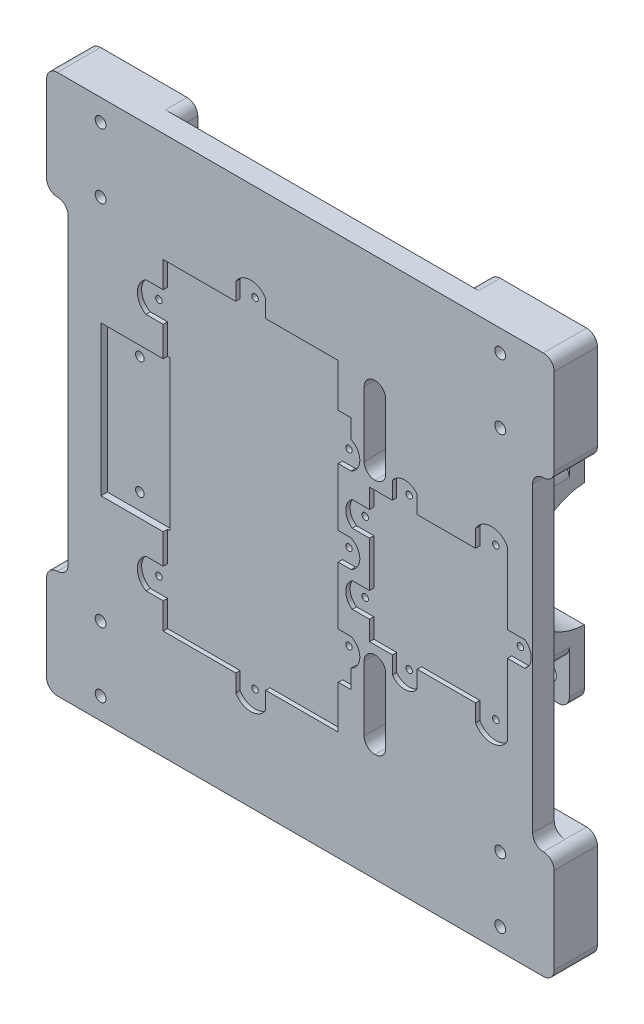
SolidWorks part; units mm, degrees
other "Marquage1"
sketch "Esquisse17" plane through (0, -52.2, -65) normal (-0.4358, -0.0146, -0.8999) x (-0.2736, 0.9547, 0.117)
ref_plane "Plan de face" through (0, 0, 0) normal (0, 0, 1) x (1, 0, 0)
ref_plane "Plan de dessus" through (0, 0, 0) normal (0, 1, 0) x (1, 0, 0)
ref_plane "Plan de droite" through (0, 0, 0) normal (1, 0, 0) x (0, 0, -1)
sketch "Esquisse1" plane through (0, 0, 0) normal (0, 0, 1) x (1, 0, 0)
  line L5 (235, 50) -> (235, 0)
  line L7 (0, 50) -> (0, 0)
  line L9 (235, 200) -> (235, 250)
  line L11 (0, 250) -> (0, 200)
  line L16 (225, 200) -> (225, 50)
  line L19 (147, 50) -> (157, 50)
  line L20 (225, 50) -> (235, 50)
  line L21 (225, 200) -> (235, 200)
  line L23 (10, 200) -> (10, 50)
  line L24 (0, 200) -> (10, 200)
  line L27 (10, 50) -> (0, 50)
  line L32 (0, 250) -> (235, 250)
  line L33 (0, 0) -> (235, 0)
  line L35 (147, 200) -> (157, 200)
  line L36 (147, 160) -> (157, 160)
  line L37 (147, 90) -> (157, 90)
  line L38 (147, 200) -> (147, 160)
  line L39 (157, 200) -> (157, 160)
  line L40 (147, 90) -> (147, 50)
  line L41 (157, 90) -> (157, 50)
  circle A0 centre (117.5, 125) radius 0.005
  dimension "D19" = 0.01
  dimension "D1" = 50
  dimension "D2" = 235
  dimension "D11" = 10
  dimension "D12" = 10
  dimension "D15" = 10
  dimension "D16" = 10
  dimension "D17" = 150
  dimension "D18" = 50
  dimension "D6" = 235
  dimension "D21" = 125
  dimension "D20" = 117.5
  dimension "D7" = 50
  dimension "D8" = 40
  dimension "D9" = 40
  dimension "D13" = 10
  dimension "D14" = 10
  dimension "D3" = 78
  dimension "D10" = 78
  dimension "D4" = 35
  dimension "D5" = 35
extrude "Boss.-Extru.2" add sketch "Esquisse1" along normal blind 10
sketch "Esquisse4" plane through (0, 0, 0) normal (0, 0, -1) x (-1, 0, 0)
  line L0 (0, 250) -> (0, 200) construction
  line L1 (0, 250) -> (-50, 250)
  line L2 (0, 250) -> (0, 200)
  line L4 (-50, 250) -> (-50, 200)
  line L5 (-117.5, 250) -> (-117.5, 0) construction
  line L6 (0, 0) -> (-235, 0) construction
  line L7 (-235, 200) -> (-185, 200)
  line L8 (-235, 250) -> (-235, 200)
  line L9 (-185, 250) -> (-185, 200)
  line L10 (-235, 250) -> (-185, 250)
  line L11 (-225, 125) -> (-10, 125) construction
  line L12 (-225, 50) -> (-225, 200) construction
  line L21 (-10, 200) -> (-10, 50) construction
  line L22 (0, 200) -> (-50, 200)
  line L24 (-235, 250) -> (0, 250) construction
  line L25 (0, 250) -> (0, 200) construction
  line L26 (-235, 50) -> (-185, 50)
  line L27 (-185, 0) -> (-185, 50)
  line L28 (-235, 0) -> (-235, 50)
  line L29 (-235, 0) -> (-185, 0)
  line L30 (0, 50) -> (-50, 50)
  line L31 (0, 0) -> (0, 50)
  line L32 (-50, 0) -> (-50, 50)
  line L33 (0, 0) -> (-50, 0)
  dimension "D1" = 50
  dimension "D2" = 50
extrude "Boss.-Extru.3" add sketch "Esquisse4" along normal blind 10
sketch "Esquisse6" plane through (0, 0, 0) normal (0, 0, -1) x (-1, 0, 0)
  line L0 (-225, 50) -> (-225, 200) construction
  line L1 (-127, 164) -> (-107, 164)
  line L2 (-127, 164) -> (-127, 86)
  line L3 (-127, 86) -> (-107, 86)
  line L4 (-107, 164) -> (-107, 86)
  line L5 (-147, 90) -> (-147, 50) construction
  line L6 (-50, 200) -> (0, 200) construction
  line L7 (-10, 50) -> (-50, 50) construction
  line L10 (-225, 200) -> (-185, 200) construction
  line L11 (-195, 164) -> (-175, 164)
  line L12 (-195, 164) -> (-195, 86)
  line L13 (-195, 86) -> (-175, 86)
  line L14 (-175, 164) -> (-175, 86)
  line L15 (-185, 50) -> (-225, 50) construction
  dimension "D5" = 36
  dimension "D6" = 36
  dimension "D1" = 20
  dimension "D8" = 30
  dimension "D3" = 36
  dimension "D4" = 36
  dimension "D7" = 50
  dimension "D2" = 20
extrude "Boss.-Extru.5" add sketch "Esquisse6" along normal blind 45
fillet "Congé1" radius 5 20 edges at (50, 250, -5) (50, 200, -5) (185, 250, -5) (185, 200, -5) (235, 50, 0) (235, 200, 0) (0, 50, 0) (0, 200, 0) (225, 50, 5) (225, 200, 5) (10, 50, 5) (10, 200, 5) (235, 250, 0) (0, 250, 0) (0, 0, 0) (235, 0, 0) (50, 50, -5) (185, 50, -5) (185, 0, -5) (50, 0, -5)
sketch "Esquisse8" plane through (195, 0, 0) normal (1, 0, 0) x (0, 0, -1)
  line L0 (22.5, 164) -> (22.5, 86) construction
  line L2 (45, 125) -> (-10, 125) construction
  line L3 (45, 164) -> (45, 86) construction
  line L4 (0, 164) -> (0, 86) construction
  line L5 (-10, 55) -> (-10, 195) construction
  line L6 (45, 164) -> (0, 164) construction
  line L7 (45, 86) -> (0, 86) construction
  circle A0 centre (45, 125) radius 28.5
  dimension "D1" = 45
  dimension "D2" = 57
extrude "Enlèv. mat.-Extru.2" cut sketch "Esquisse8" against normal blind 100
sketch "Esquisse12" plane through (0, 164, 0) normal (0, 1, 0) x (1, 0, 0)
  line L10 (127, 45) -> (127, 0) construction
  line L11 (107, 45) -> (127, 45)
  line L12 (107, 45) -> (107, 37)
  line L13 (107, 37) -> (127, 37)
  line L14 (127, 45) -> (127, 37)
  line L15 (195, 45) -> (195, 0) construction
  line L16 (175, 45) -> (195, 45)
  line L17 (175, 45) -> (175, 37)
  line L18 (175, 37) -> (195, 37)
  line L19 (195, 45) -> (195, 37)
  dimension "D1" = 8
  dimension "D2" = 8
extrude "Boss.-Extru.6" add sketch "Esquisse12" along normal blind 20
sketch "Esquisse13" plane through (0, 86, 0) normal (0, -1, 0) x (1, 0, 0)
  line L0 (127, -45) -> (127, 0) construction
  line L1 (107, -45) -> (127, -45)
  line L2 (107, -45) -> (107, -37)
  line L3 (107, -37) -> (127, -37)
  line L4 (127, -45) -> (127, -37)
  line L5 (195, -45) -> (195, 0) construction
  line L6 (175, -45) -> (195, -45)
  line L7 (175, -45) -> (175, -37)
  line L8 (175, -37) -> (195, -37)
  line L9 (195, -45) -> (195, -37)
  dimension "D1" = 8
  dimension "D2" = 8
extrude "Boss.-Extru.7" add sketch "Esquisse13" along normal blind 20
fillet "Congé55" radius 5 16 edges at (107, 184, -41) (175, 184, -41) (175, 66, -41) (107, 66, -41) (127, 66, -41) (195, 66, -41) (175, 164, -18.5) (195, 164, -18.5) (127, 164, -18.5) (107, 164, -18.5) (107, 86, -18.5) (127, 86, -18.5) (175, 86, -18.5) (195, 86, -18.5) (195, 184, -41) (127, 184, -41)
sketch "Esquisse14" plane through (0, 0, -45) normal (0, 0, -1) x (-1, 0, 0)
  line L0 (-175, 153.5) -> (-127, 153.5) construction
  line L1 (-151, 153.5) -> (-151, 184.1356) construction
  line L2 (-175, 153.5) -> (-175, 179) construction
  line L3 (-195, 125) -> (-107, 125) construction
  line L4 (-195, 159) -> (-195, 91) construction
  line L5 (-107, 91) -> (-107, 159) construction
  circle A0 centre (-185, 173.5) radius 4
  circle A1 centre (-117, 173.5) radius 4
  circle A2 centre (-117, 76.5) radius 4
  circle A3 centre (-185, 76.5) radius 4
  dimension "D1" = 8
  dimension "D2" = 20
  dimension "D3" = 10
extrude "Enlèv. mat.-Extru.4" cut sketch "Esquisse14" against normal blind 10
sketch "Esquisse15" plane through (0, 66, 0) normal (0, -1, 0) x (1, 0, 0)
  line L5 (195, -37) -> (195, -45) construction
  line L6 (175, -45) -> (195, -45)
  line L7 (175, -45) -> (175, -44)
  line L8 (175, -44) -> (195, -44)
  line L9 (195, -45) -> (195, -44)
  dimension "D1" = 1
extrude "Enlèv. mat.-Extru.5" cut sketch "Esquisse15" against normal blind 120
sketch "Esquisse22" plane through (0, 0, 0) normal (0, 0, 1) x (1, 0, 0)
  line L0 (117.5, 250) -> (117.5, 0) construction
  line L1 (230, 250) -> (5, 250) construction
  line L2 (5, 0) -> (230, 0) construction
  line L3 (117.5, 0) -> (225, 125) construction
  line L4 (225, 55) -> (225, 195) construction
  line L5 (225, 125) -> (10, 125) construction
  line L6 (10, 195) -> (10, 55) construction
  line L7 (12.5, 240) -> (37.5, 240) construction
  line L8 (12.5, 245) -> (37.5, 245)
  line L9 (12.5, 235) -> (37.5, 235)
  line L10 (12.5, 210) -> (37.5, 210) construction
  line L11 (12.5, 215) -> (37.5, 215)
  line L12 (12.5, 205) -> (37.5, 205)
  line L13 (0, 245) -> (0, 205) construction
  line L16 (5, 200) -> (55.9669, 200) construction
  line L19 (12.5, 40) -> (37.5, 40) construction
  line L20 (12.5, 35) -> (37.5, 35)
  line L21 (12.5, 45) -> (37.5, 45)
  line L22 (12.5, 10) -> (37.5, 10) construction
  line L23 (12.5, 5) -> (37.5, 5)
  line L24 (12.5, 15) -> (37.5, 15)
  line L25 (222.5, 10) -> (197.5, 10) construction
  line L26 (222.5, 5) -> (197.5, 5)
  line L27 (222.5, 15) -> (197.5, 15)
  line L28 (222.5, 40) -> (197.5, 40) construction
  line L29 (222.5, 35) -> (197.5, 35)
  line L30 (222.5, 45) -> (197.5, 45)
  line L31 (222.5, 240) -> (197.5, 240) construction
  line L32 (222.5, 245) -> (197.5, 245)
  line L33 (222.5, 235) -> (197.5, 235)
  line L34 (222.5, 210) -> (197.5, 210) construction
  line L35 (222.5, 215) -> (197.5, 215)
  line L36 (222.5, 205) -> (197.5, 205)
  arc A0 (12.5, 245) -> (12.5, 235) centre (12.5, 240) ccw
  arc A1 (37.5, 235) -> (37.5, 245) centre (37.5, 240) ccw
  arc A2 (12.5, 215) -> (12.5, 205) centre (12.5, 210) ccw
  arc A3 (37.5, 205) -> (37.5, 215) centre (37.5, 210) ccw
  arc A8 (12.5, 35) -> (12.5, 45) centre (12.5, 40) cw
  arc A9 (37.5, 45) -> (37.5, 35) centre (37.5, 40) cw
  arc A10 (12.5, 5) -> (12.5, 15) centre (12.5, 10) cw
  arc A11 (37.5, 15) -> (37.5, 5) centre (37.5, 10) cw
  arc A12 (222.5, 5) -> (222.5, 15) centre (222.5, 10) ccw
  arc A13 (197.5, 15) -> (197.5, 5) centre (197.5, 10) ccw
  arc A14 (222.5, 35) -> (222.5, 45) centre (222.5, 40) ccw
  arc A15 (197.5, 45) -> (197.5, 35) centre (197.5, 40) ccw
  arc A16 (222.5, 245) -> (222.5, 235) centre (222.5, 240) cw
  arc A17 (197.5, 235) -> (197.5, 245) centre (197.5, 240) cw
  arc A18 (222.5, 215) -> (222.5, 205) centre (222.5, 210) cw
  arc A19 (197.5, 205) -> (197.5, 215) centre (197.5, 210) cw
  point P14 (25, 240)
  point P19 (25, 210)
  point P32 (25, 40)
  point P39 (25, 10)
  point P47 (210, 10)
  point P54 (210, 40)
  point P61 (210, 240)
  point P68 (210, 210)
  dimension "D3" = 5
  dimension "D4" = 5
  dimension "D1" = 25
  dimension "D2" = 25
  dimension "D5" = 25
  dimension "D6" = 25
  dimension "D7" = 10
  dimension "D8" = 10
extrude "Enlèv. mat.-Extru.9" cut sketch "Esquisse22" against normal blind 10
sketch "Esquisse23" plane through (0, 0, 0) normal (0, 0, 1) x (1, 0, 0)
  line L0 (117.5, 250) -> (117.5, 0) construction
  line L1 (230, 250) -> (5, 250) construction
  line L2 (5, 0) -> (230, 0) construction
  line L3 (117.5, 0) -> (225, 125) construction
  line L4 (225, 55) -> (225, 195) construction
  line L5 (225, 125) -> (10, 125) construction
  line L6 (10, 195) -> (10, 55) construction
  line L7 (0, 245) -> (0, 205) construction
  line L8 (5, 200) -> (40.2929, 200) construction
  circle A0 centre (25, 240) radius 2.5
  circle A1 centre (25, 210) radius 2.5
  circle A3 centre (25, 40) radius 2.5
  circle A4 centre (25, 10) radius 2.5
  circle A5 centre (210, 10) radius 2.5
  circle A6 centre (210, 40) radius 2.5
  circle A7 centre (210, 210) radius 2.5
  circle A8 centre (210, 240) radius 2.5
  dimension "D1" = 25
  dimension "D2" = 10
  dimension "D3" = 25
  dimension "D4" = 10
  dimension "D5" = 5
  dimension "D6" = 5
extrude "Enlèv. mat.-Extru.10" cut sketch "Esquisse23" along normal blind 10
sketch "Esquisse40" plane through (0, 0, 10) normal (0, 0, 1) x (1, 0, 0)
  line L1 (55.1716, 159.6716) -> (25.1716, 159.6716)
  line L2 (55.1716, 159.6716) -> (55.1716, 90.3284)
  line L3 (55.1716, 90.3284) -> (25.1716, 90.3284)
  line L4 (25.1716, 159.6716) -> (25.1716, 90.3284)
  line L5 (10, 195) -> (10, 55) construction
  line L6 (230, 250) -> (5, 250) construction
  dimension "D1" = 30
  dimension "D2" = 15.1716
  dimension "D3" = 90.3284
  dimension "D4" = 69.3431
extrude "Enlèv. mat.-Extru.27" cut sketch "Esquisse40" against normal blind 3
sketch "Esquisse41" plane through (0, 0, 7) normal (0, 0, 1) x (1, 0, 0)
  line L0 (55.1716, 159.6716) -> (25.1716, 159.6716) construction
  line L2 (55.1716, 90.3284) -> (55.1716, 159.6716) construction
  line L3 (25.1716, 125) -> (55.1716, 125) construction
  circle A0 centre (40.1716, 152.1716) radius 2
  circle A2 centre (40.1716, 97.8284) radius 2
  dimension "D1" = 7.5
  dimension "D4" = 4
  dimension "D5" = 15
extrude "Enlèv. mat.-Extru.28" cut sketch "Esquisse41" against normal blind 10
sketch "Esquisse43" plane through (0, 0, 10) normal (0, 0, 1) x (1, 0, 0)
  line L142 (54, 187.3564) -> (54, 199.5)
  line L143 (54, 199.5) -> (87.5718, 199.5)
  line L144 (101.4282, 199.5) -> (135, 199.5)
  line L145 (135, 199.5) -> (135, 179.5)
  line L151 (225, 55) -> (225, 195) construction
  line L152 (87.5718, 199.5) -> (87.5718, 207.5)
  line L154 (101.4282, 207.5) -> (101.4282, 199.5)
  line L187 (25.1716, 125) -> (213.3561, 125) construction
  line L208 (135, 70.5) -> (135, 50.5)
  line L209 (101.4282, 50.5) -> (135, 50.5)
  line L220 (149.5, 156) -> (160.0973, 156)
  line L244 (87.5718, 203.5) -> (101.4282, 203.5) construction
  line L247 (54, 187.3564) -> (46, 187.3564)
  line L249 (46, 173.5) -> (54, 173.5)
  line L251 (25.1716, 159.6716) -> (25.1716, 90.3284) construction
  line L256 (50, 187.3564) -> (50, 173.5) construction
  line L260 (135, 179.5) -> (141, 179.5)
  line L262 (138, 179.5) -> (138, 70.5) construction
  line L263 (54, 173.5) -> (54, 76.5)
  line L264 (46, 76.5) -> (54, 76.5)
  line L269 (135, 70.5) -> (141, 70.5)
  line L281 (213.3561, 130.7446) -> (221.3561, 130.7446)
  line L282 (213.3561, 125) -> (224.3561, 125) construction
  line L284 (217.3561, 130.7446) -> (217.3561, 119.2554) construction
  line L285 (160.0973, 156) -> (160.0973, 164)
  line L287 (149.5, 156) -> (149.5, 147)
  line L294 (213.3561, 119.2554) -> (221.3561, 119.2554)
  line L302 (171.5864, 164) -> (171.5864, 156)
  line L303 (160.0973, 160) -> (171.5864, 160) construction
  line L316 (198.5864, 156) -> (198.5864, 164)
  line L319 (198.5864, 160) -> (213.3561, 160) construction
  line L325 (141, 179.5) -> (141, 70.5) construction
  line L326 (141, 179.5) -> (141, 170.8246)
  line L327 (141, 70.5) -> (141, 79.1754)
  line L329 (198.5864, 94) -> (198.5864, 86)
  line L330 (171.5864, 86) -> (171.5864, 94)
  line L332 (149.5, 147) -> (141.5, 147)
  line L333 (141.5, 147) -> (141.5, 135.5109) construction
  line L336 (149.5, 135.5109) -> (149.5, 114.4891)
  line L337 (145.5, 147) -> (145.5, 135.5109) construction
  line L338 (141.5, 114.4891) -> (149.5, 114.4891)
  line L339 (149.5, 94) -> (149.5, 103)
  line L340 (149.5, 103) -> (141.5, 103)
  line L341 (160.0973, 94) -> (160.0973, 86)
  line L342 (149.5, 94) -> (160.0973, 94)
  line L343 (54, 62.6436) -> (46, 62.6436)
  line L344 (54, 50.5) -> (54, 62.6436)
  line L345 (54, 50.5) -> (87.5718, 50.5)
  line L346 (87.5718, 50.5) -> (87.5718, 42.5)
  line L347 (101.4282, 42.5) -> (101.4282, 50.5)
  line L349 (141.5, 135.5109) -> (149.5, 135.5109)
  line L350 (141, 158.1754) -> (135, 158.1754)
  line L351 (141, 118.6754) -> (135, 118.6754)
  line L355 (135, 158.1754) -> (135, 131.3246)
  line L356 (135, 131.3246) -> (141, 131.3246)
  line L357 (135, 118.6754) -> (135, 91.8246)
  line L358 (135, 91.8246) -> (141, 91.8246)
  line L360 (171.5864, 156) -> (198.5864, 156)
  line L361 (171.5864, 94) -> (198.5864, 94)
  line L362 (213.3561, 164) -> (213.3561, 86) construction
  line L363 (213.3561, 164) -> (213.3561, 130.7446)
  line L364 (213.3561, 119.2554) -> (213.3561, 86)
  line L365 (55.1716, 159.6716) -> (25.1716, 159.6716) construction
  line L366 (10, 195) -> (10, 55) construction
  circle A55 centre (94.5, 203.5) radius 1.5
  circle A56 centre (50, 180.4282) radius 1.5
  circle A57 centre (138, 164.5) radius 1.5
  circle A58 centre (138, 85.5) radius 1.5
  circle A61 centre (138, 125) radius 1.5
  circle A62 centre (217.3561, 125) radius 1.5
  circle A67 centre (165.8419, 160) radius 1.5
  circle A71 centre (205.9713, 160) radius 1.5
  arc A73 (141, 170.8246) -> (141, 158.1754) centre (138, 164.5) cw
  arc A74 (141, 91.8246) -> (141, 79.1754) centre (138, 85.5) cw
  arc A75 (141, 131.3246) -> (141, 118.6754) centre (138, 125) cw
  circle A76 centre (145.5, 141.2554) radius 1.5
  circle A78 centre (145.5, 108.7446) radius 1.5
  arc A79 (141.5, 103) -> (141.5, 114.4891) centre (145.5, 108.7446) cw
  arc A80 (160.0973, 164) -> (171.5864, 164) centre (165.8419, 160) cw
  arc A81 (198.5864, 164) -> (213.3561, 164) centre (205.9713, 160) cw
  arc A82 (221.3561, 130.7446) -> (221.3561, 119.2554) centre (217.3561, 125) cw
  circle A83 centre (205.9713, 90) radius 1.5
  arc A84 (198.5864, 86) -> (213.3561, 86) centre (205.9713, 90) ccw
  circle A85 centre (165.8419, 90) radius 1.5
  arc A86 (160.0973, 86) -> (171.5864, 86) centre (165.8419, 90) ccw
  arc A87 (87.5718, 207.5) -> (101.4282, 207.5) centre (94.5, 203.5) cw
  arc A88 (46, 187.3564) -> (46, 173.5) centre (50, 180.4282) ccw
  circle A89 centre (50, 69.5718) radius 1.5
  arc A90 (46, 62.6436) -> (46, 76.5) centre (50, 69.5718) cw
  circle A91 centre (94.5, 46.5) radius 1.5
  arc A92 (87.5718, 42.5) -> (101.4282, 42.5) centre (94.5, 46.5) ccw
  arc A93 (141.5, 147) -> (141.5, 135.5109) centre (145.5, 141.2554) ccw
  point P3 (0, 0)
  point P76 (149.5, 125)
  point P78 (224.3561, 125)
  point P96 (54, 125)
  point P143 (138, 125)
  point P156 (54, 125)
  dimension "D6" = 10.5973
  dimension "D12" = 7
  dimension "D15" = 8
  dimension "D17" = 3
  dimension "D18" = 7
  dimension "D20" = 7
  dimension "D21" = 7
  dimension "D4" = 8
  dimension "D5" = 3
  dimension "D7" = 3
  dimension "D8" = 8.3986
  dimension "D9" = 8
  dimension "D10" = 7
  dimension "D11" = 7
  dimension "D25" = 3
  dimension "D35" = 21.0217
  dimension "D26" = 3
  dimension "D32" = 3
  dimension "D33" = 15
  dimension "D13" = 3
  dimension "D14" = 1.5
  dimension "D23" = 8
  dimension "D16" = 8
  dimension "D19" = 8
  dimension "D22" = 33.5718
  dimension "D24" = 9
  dimension "D27" = 8
  dimension "D28" = 27
  dimension "D29" = 13.8284
  dimension "D30" = 6
  dimension "D31" = 20
  dimension "D34" = 8
  dimension "D36" = 44
  dimension "D37" = 12.1436
  dimension "D38" = 33.5718
  dimension "D39" = 26.8509
  dimension "D40" = 6
  dimension "D41" = 74.5
  dimension "D42" = 26.8509
  dimension "D43" = 90
  dimension "D44" = 6
  dimension "D45" = 31
  dimension "D46" = 11.6439
  dimension "D47" = 10.5973
extrude "Enlèv. mat.-Extru.29" cut sketch "Esquisse43" against normal blind 2
sketch "Esquisse45" plane through (0, 0, 10) normal (0, 0, 1) x (1, 0, 0)
  circle A0 centre (94.5, 203.5) radius 1.5
  circle A1 centre (50, 180.4282) radius 1.5
  circle A2 centre (138, 164.5) radius 1.5
  circle A3 centre (145.5, 141.2554) radius 1.5
  circle A4 centre (165.8419, 160) radius 1.5
  circle A5 centre (205.9713, 160) radius 1.5
  circle A6 centre (217.3561, 125) radius 1.5
  circle A7 centre (145.5, 108.7446) radius 1.5
  circle A8 centre (165.8419, 90) radius 1.5
  circle A9 centre (205.9713, 90) radius 1.5
  circle A10 centre (138, 85.5) radius 1.5
  circle A11 centre (138, 125) radius 1.5
  circle A12 centre (94.5, 46.5) radius 1.5
  circle A13 centre (50, 69.5718) radius 1.5
extrude "Enlèv. mat.-Extru.30" cut sketch "Esquisse45" against normal blind 10
fillet "Congé56" radius 5 8 edges at (147, 50, 5) (157, 50, 5) (157, 90, 5) (147, 90, 5) (157, 160, 5) (147, 160, 5) (157, 200, 5) (147, 200, 5)
equation "\"D15@Esquisse1\"=\"D11@Esquisse1\""
equation "\"D16@Esquisse1\"=\"D12@Esquisse1\""
equation "\"D18@Esquisse1\"=\"D1@Esquisse1\""
equation "\"D12@Esquisse1\"=\"D11@Esquisse1\""
equation "\"D5@Esquisse6\"=\"D3@Esquisse6\""
equation "\"D6@Esquisse6\"=\"D3@Esquisse6\""
equation "\"D2@Esquisse13\"=\"D1@Esquisse13\""
equation "\"D2@Esquisse12\"=\"D1@Esquisse12\""
equation "\"D21@Esquisse1\"=(\"D1@Esquisse1\"+\"D17@Esquisse1\"+\"D7@Esquisse1\")/2"
equation "\"D6@Esquisse1\"=\"D2@Esquisse1\""
equation "\"D20@Esquisse1\"=\"D2@Esquisse1\"/2"
equation "\"D2@Esquisse4\"=\"D1@Esquisse4\""
equation "\"D7@Esquisse1\"=\"D1@Esquisse1\""
equation "\"D4@Esquisse6\"=\"D3@Esquisse6\""
equation "\"D9@Esquisse1\"=\"D8@Esquisse1\""
equation "\"D14@Esquisse1\"=\"D13@Esquisse1\""
equation "\"D10@Esquisse1\"=\"D3@Esquisse1\""
